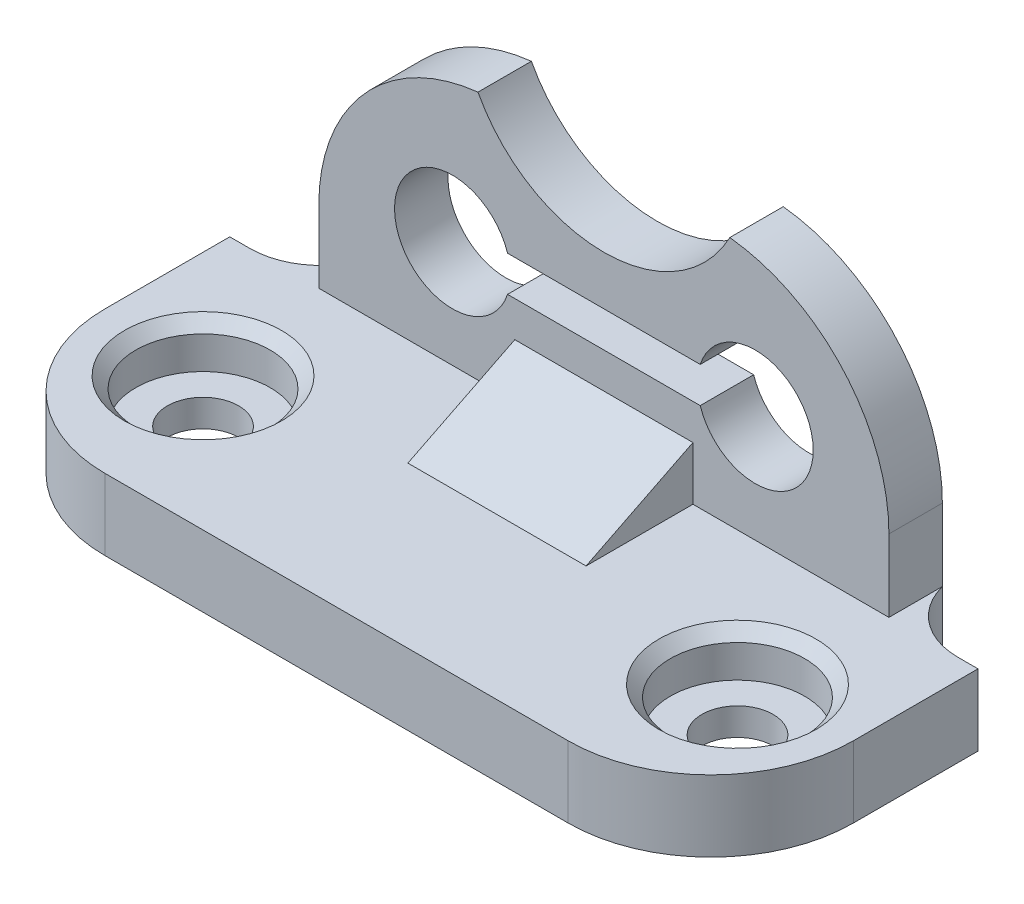
SolidWorks part; units mm, degrees
ref_plane "Alzado" through (0, 0, 0) normal (0, 0, 1) x (1, 0, 0)
ref_plane "Planta" through (0, 0, 0) normal (0, 1, 0) x (1, 0, 0)
ref_plane "Vista lateral" through (0, 0, 0) normal (1, 0, 0) x (0, 0, -1)
sketch "Croquis1" plane through (0, 0, 0) normal (0, 0, 1) x (1, 0, 0)
  line L1 (0, -9) -> (-16, -9)
  line L2 (-16, -9) -> (-16, 9)
  line L3 (-16, 9) -> (0, 9)
  line L6 (0, 9) -> (0, -9)
  line L7 (-8.5, 15) -> (-8.5, -15) construction
  line L8 (0, 21.0134) -> (0, -17.4201) construction
  line L9 (16, 9) -> (0, 9)
  line L10 (16, -9) -> (16, 9)
  line L11 (0, -9) -> (16, -9)
  circle A1 centre (-8.5, 1) radius 3.25
  circle A2 centre (8.5, 1) radius 3.25
  circle A3 centre (0, 12.1243) radius 6 construction
  circle A4 centre (-8.5, 1) radius 8 construction
  circle A5 centre (8.5, 1) radius 8 construction
  point P0 (0, 0)
  point P20 (0, 0)
  dimension "D3" = 10
  dimension "D2" = 6.5
  dimension "D4" = 12
  dimension "D6" = 16
  dimension "D7" = 16
  dimension "D8" = 8.5
  dimension "D1" = 16
  dimension "D5" = 18
extrude "Saliente-Extruir1" add sketch "Croquis1" along normal blind 3 contours L6 L3 L2 L1 A1 | L6 L11 L10 L9 A2 region at (-8, -8.7592, 0) region at (0.2408, 0, 0)
sketch "Croquis2" plane through (0, 0, 3) normal (0, 0, 1) x (1, 0, 0)
  line L0 (0, 12.7473) -> (0, 0) construction
  line L1 (-8.5, 1) -> (8.5, 1) construction
  line L3 (-7.5, 2) -> (7.5, 2)
  line L4 (-7.5, 2) -> (-7.5, 0)
  line L5 (-7.5, 0) -> (7.5, 0)
  line L6 (7.5, 2) -> (7.5, 0)
  line L7 (-7.5, 2) -> (7.5, 0) construction
  line L8 (-7.5, 0) -> (7.5, 2) construction
  circle A0 centre (-8.5, 1) radius 3.25 construction
  circle A1 centre (-8.5, 1) radius 3.25
  circle A2 centre (8.5, 1) radius 3.25 construction
  circle A3 centre (8.5, 1) radius 3.25
  circle A4 centre (-8.5, 1) radius 6.5 construction
  circle A5 centre (8.5, 1) radius 6.5 construction
  circle A6 centre (0, 12.7473) radius 8
  point P12 (0, 1)
  line M10 (16, 9) -> (-16, 9)
  dimension "D1" = 13
  dimension "D2" = 16
  dimension "D3" = 2
  dimension "D4" = 15
extrude "Cortar-Extruir1" cut sketch "Croquis2" against normal blind 3 contours A6 M10 | A6 M10 | L5 L6 L3 L4 region at (0, 14.2352, 3) region at (0, 7.253, 3)
fillet "Redondeo1" radius 10 2 edges at (16, 9, 1.5) (-16, 9, 1.5)
sketch "Croquis3" plane through (0, 0, 0) normal (1, 0, 0) x (0, 0, -1)
  line L1 (-3, -9) -> (-18, -9)
  line L2 (-3, -9) -> (-3, -5)
  line L3 (-3, -5) -> (-18, -5)
  line L4 (-18, -9) -> (-18, -5)
  dimension "D1" = 4
  dimension "D2" = 15
extrude "Saliente-Extruir2" add sketch "Croquis3" along normal mid plane 42
sketch "Croquis4" plane through (0, -5, 0) normal (0, 1, 0) x (1, 0, 0)
  line L0 (-21, -10.5) -> (21, -10.5) construction
  line L1 (-21, -3) -> (-21, -18) construction
  line L2 (21, -3) -> (21, -18) construction
  line L4 (0, -5.9142) -> (0, -19.1557) construction
  circle A0 centre (0, -10.5) radius 2 construction
  circle A1 centre (-15, -10.5) radius 2
  circle A2 centre (15, -10.5) radius 2
  point P10 (0, -10.5)
  dimension "D1" = 4
  dimension "D3" = 4
  dimension "D2" = 15
extrude "Cortar-Extruir2" cut sketch "Croquis4" against normal blind 32
fillet "Redondeo2" radius 8 2 edges at (21, -7, 18) (-21, -7, 18)
hole_wizard "Refrentado para tornillo con cabeza troncocónica de #61" positions "Croquis3D2" profile "Croquis5" counterbore size "#6" standard "Ansi Inch" end condition through all
sketch3d "Croquis3D2"
  line L0 (-15, -9, 10.5) -> (-15, -5, 10.5) construction
  line L1 (15, -9, 10.5) -> (15, -5, 10.5) construction
  point P0 (-15, -5, 10.5)
  point P4 (15, -5, 10.5)
sketch "Croquis5" plane through (-15, -5, 10.5) normal (1, 0, 0) x (0, 0, 1)
  line L0 (0, 0) -> (0, 4)
  line L1 (0, 4) -> (1.8986, 4)
  line L3 (1.8986, 4) -> (1.8986, 2.4638)
  line L4 (3.7706, 2.4638) -> (1.8986, 2.4638)
  line L5 (3.7706, 2.4638) -> (3.7706, 0.635)
  line L6 (3.7706, 0.635) -> (4.4056, 0)
  line L7 (4.4056, 0) -> (0, 0)
  line L8 (-3.7706, 0.635) -> (-4.4056, 0) construction
  line L11 (0, -6.35) -> (0, 107.95) construction
  dimension "Diámetro de taladro hasta el siguiente" = 3.7973
  dimension "Profundidad de taladro hasta el siguiente" = 4
  dimension "Diámetro de refrentado" = 7.5413
  dimension "Profundidad de refrentado" = 2.4638
  dimension "Diámetro de avellanado cercano" = 8.8113
  dimension "Ángulo de avellanado cercano" = 90
sketch "Croquis6" plane through (0, 0, 0) normal (1, 0, 0) x (0, 0, -1)
  line L0 (-3, -2) -> (-9, -5)
  line L1 (-3, -5) -> (-3, -0.9428) construction
  line L2 (-3, -5) -> (-10, -5) construction
  dimension "D1" = 3
  dimension "D2" = 6
rib "Nervio1" sketch "Croquis6" sketch "Croquis6" thickness 10 extrusion direction parallel to sketch draft on no parameters "D1"=10
fillet "Redondeo3" radius 4 2 edges at (16, -7, 3) (-16, -7, 3)
